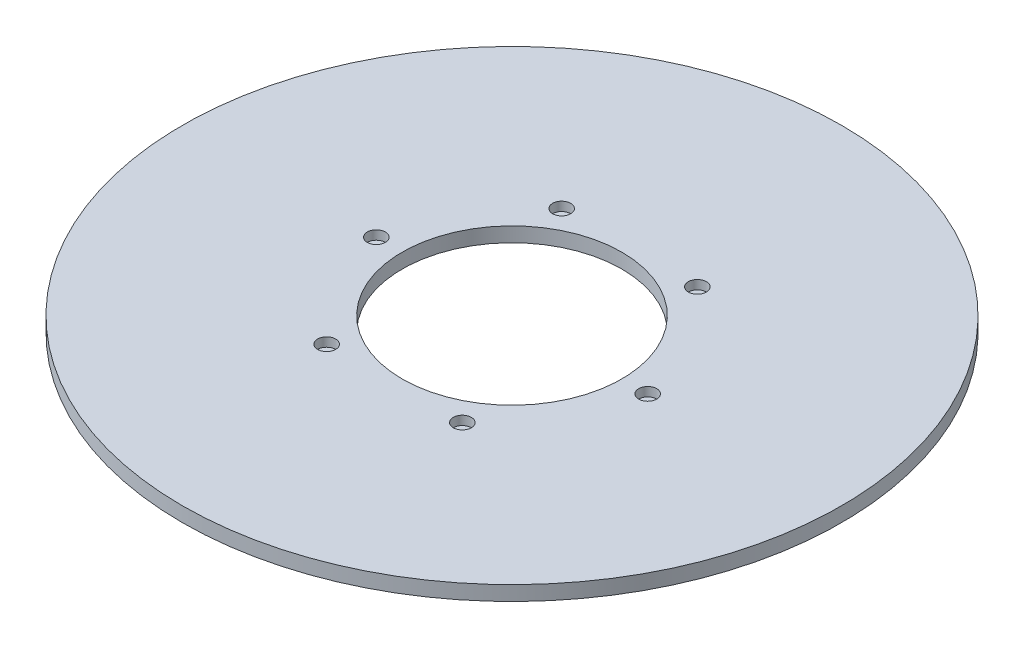
SolidWorks part; units mm, degrees
ref_plane "Front Plane" through (0, 0, 0) normal (0, 0, 1) x (1, 0, 0)
ref_plane "Top Plane" through (0, 0, 0) normal (0, 1, 0) x (1, 0, 0)
ref_plane "Right Plane" through (0, 0, 0) normal (1, 0, 0) x (0, 0, -1)
sketch "Sketch1" plane through (0, 0, 0) normal (0, 1, 0) x (1, 0, 0)
  circle A0 centre (0, 0) radius 90
  dimension "FLANGE_OD" = 180
extrude "Boss-Extrude1" add sketch "Sketch1" along normal blind 4
sketch "Sketch2" plane through (0, 0, 0) normal (0, 1, 0) x (1, 0, 0)
  circle A0 centre (0, 0) radius 30
  dimension "BORE_D" = 60
extrude "Cut-Extrude1" cut sketch "Sketch2" along normal through all
sketch "Sketch3" plane through (0, 4, 0) normal (0, 1, 0) x (1, 0, 0)
  circle A0 centre (0, 0) radius 37.0565 construction
  circle A1 centre (-37.0565, 0) radius 2.4689
  dimension "BOLT_D" = 4.9378
  dimension "BOLT_PCD" = 74.1131
extrude "Cut-Extrude2" cut sketch "Sketch3" against normal blind 2.4594
pattern_circular "CirPattern1" count 6 over 360 about axis through (0, 0, 0) along (0, 1, 0) of "Cut-Extrude2"
